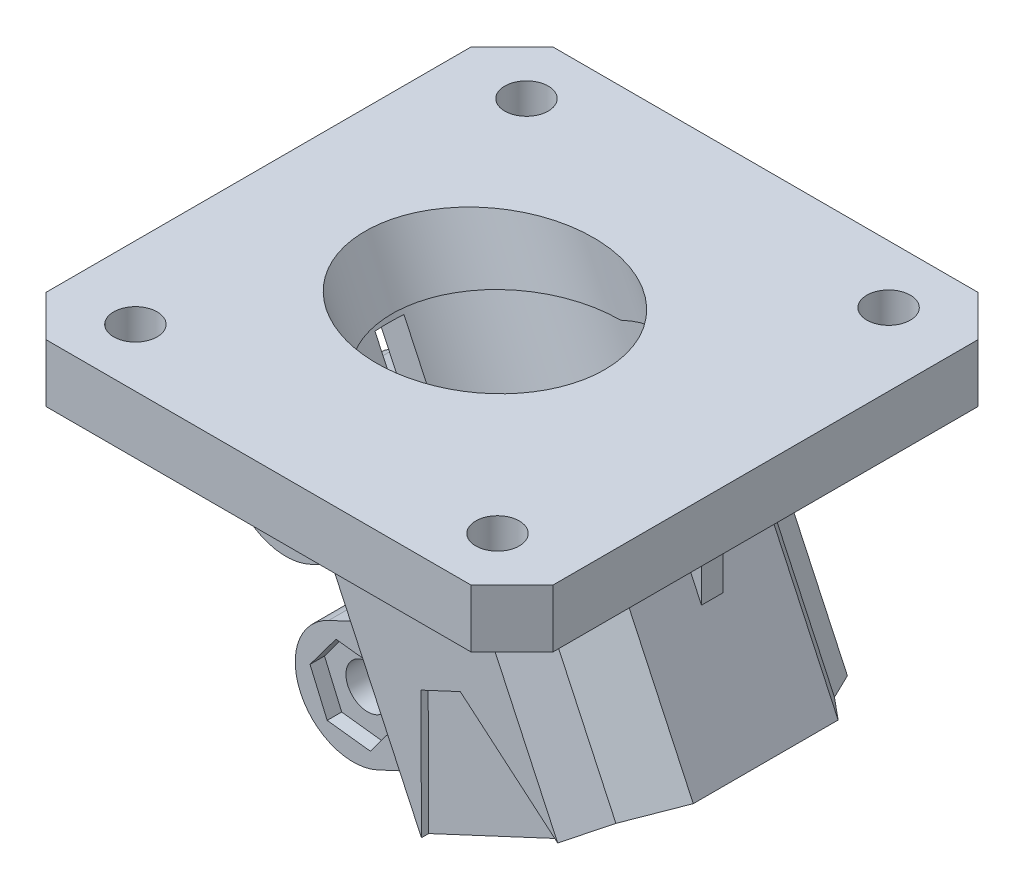
SolidWorks part; units mm, degrees
ref_plane "Front Plane" through (0, 0, 0) normal (0, 0, 1) x (1, 0, 0)
ref_plane "Top Plane" through (0, 0, 0) normal (0, 1, 0) x (1, 0, 0)
ref_plane "Right Plane" through (0, 0, 0) normal (1, 0, 0) x (0, 0, -1)
sketch "Sketch1" plane through (0, 0, 0) normal (0, 1, 0) x (1, 0, 0)
  line L0 (-17.5, 14.6716) -> (-14.6716, 17.5)
  line L1 (14.6716, -17.5) -> (-14.6716, -17.5)
  line L2 (17.5, -14.6716) -> (17.5, 14.6716)
  line L3 (14.6716, 17.5) -> (-14.6716, 17.5)
  line L4 (-17.5, -14.6716) -> (-17.5, 14.6716)
  line L5 (17.5, -17.5) -> (-17.5, 17.5) construction
  line L6 (17.5, 17.5) -> (-17.5, -17.5) construction
  line L7 (14.6716, 17.5) -> (17.5, 14.6716)
  line L8 (17.5, -14.6716) -> (14.6716, -17.5)
  line L9 (-14.6716, -17.5) -> (-17.5, -14.6716)
  point P0 (0, 0)
  point P17 (0, 0)
  dimension "D1" = 35
  dimension "D2" = 35
  dimension "D3" = 4
  dimension "D4" = 4
extrude "Boss-Extrude1" add sketch "Sketch1" along normal blind 4
sketch "Sketch2" plane through (0, 4, 0) normal (0, 1, 0) x (1, 0, 0)
  line L0 (-12.5, 13.5) -> (-12.5, -13.5) construction
  line L1 (-12.5, 13.5) -> (12.5, 13.5) construction
  circle A0 centre (-12.5, 13.5) radius 1.5
  circle A1 centre (12.5, 13.5) radius 1.5
  circle A2 centre (-12.5, -13.5) radius 1.5
  circle A3 centre (12.5, -13.5) radius 1.5
  point P8 (-12.5, 0)
  point P9 (0, 13.5)
  dimension "D3" = 3
  dimension "D4" = 3
  dimension "D5" = 3
  dimension "D6" = 3
  dimension "D1" = 25
  dimension "D2" = 27
  dimension "D7" = 27
  dimension "D8" = 25
extrude "Cut-Extrude1" cut sketch "Sketch2" against normal through all
sketch "Sketch3" plane through (0, 0, 0) normal (0, 0, 1) x (1, 0, 0)
  line L0 (-14.6716, 0) -> (14.6716, 0) construction
  line L2 (-14.6716, 0) -> (14.6716, 0)
  line L3 (0, 0) -> (8.4524, -18.1262)
  dimension "D1" = 65
  dimension "D2" = 20
ref_plane "Plane1" through (8.4524, -18.1262, 0) normal (0.4226, -0.9063, 0) x (-0.9063, -0.4226, 0)
sketch "Sketch4" plane through (8.4524, -18.1262, 0) normal (0.4226, -0.9063, 0) x (-0.9063, -0.4226, 0)
  line L0 (10, 5) -> (10, -5)
  line L1 (10, 5) -> (6.9136, 7.5444)
  line L2 (6.9136, 7.5444) -> (5.1902, 10)
  line L5 (0, 0) -> (10, 0) construction
  line L6 (0, 0) -> (0, 9) construction
  line L7 (-10, 5) -> (-10, -5)
  line L8 (-10, 5) -> (-6.9136, 7.5444)
  line L9 (-6.9136, 7.5444) -> (-5.1902, 10)
  line L11 (10, -5) -> (6.9136, -7.5444)
  line L12 (6.9136, -7.5444) -> (5.1902, -10)
  line L16 (-6.9136, -7.5444) -> (-5.1902, -10)
  line L17 (-10, -5) -> (-6.9136, -7.5444)
  line L18 (-5.1902, 10) -> (5.1902, 10)
  line L19 (-5.1902, -10) -> (5.1902, -10)
  circle A0 centre (0, 0) radius 8
  point P6 (10, 0)
  point P23 (-10, 0)
  dimension "D1" = 16
  dimension "D2" = 10
  dimension "D3" = 10
  dimension "D4" = 3
  dimension "D6" = 4
  dimension "D7" = 10
extrude "Boss-Extrude2" add sketch "Sketch4" against normal up to surface (16.2695 mm away) up to face at (12.5, 0, -12)
sketch "Sketch5" plane through (8.4524, -18.1262, 0) normal (0.4226, -0.9063, 0) x (-0.9063, -0.4226, 0)
  circle A0 centre (0, 0) radius 8 construction
  circle A1 centre (0, 0) radius 8
extrude "Cut-Extrude2" cut sketch "Sketch5" against normal blind 20
sketch "Sketch7" plane through (0, 0, 0) normal (0, 0, 1) x (1, 0, 0)
  line L0 (11.0338, 0) -> (17.5154, -13.9) construction
  line L1 (11.0338, 0) -> (13.8316, -6)
  line L2 (-14.6716, 0) -> (14.6716, 0) construction
  line L3 (11.0338, 0) -> (13.8316, 0)
  line L4 (13.8316, 0) -> (13.8316, -6)
  dimension "D1" = 6
extrude "Boss-Extrude3" add sketch "Sketch7" along normal blind 0.75 and the other way blind 0.75
sketch "Sketch8" plane through (0, 0, 0) normal (0, 0, 1) x (1, 0, 0)
  line L0 (-11.0338, 0) -> (-0.6107, -22.3523) construction
  line L1 (-11.0338, 0) -> (-0.6107, -22.3523)
  line L2 (-14.6716, 0) -> (14.6716, 0) construction
  line L3 (-14.6716, 0) -> (14.6716, 0)
  line L4 (-8.9207, -4.5315) -> (-12.0928, -6.0107)
  line L5 (-9.1344, -12.3549) -> (-5.9624, -10.8757)
  line L6 (-7.444, -15.9801) -> (-4.2719, -14.5009)
  line L7 (-4.4856, -22.3242) -> (-1.3136, -20.8451)
  line L8 (2.1865, -21.048) -> (-0.6107, -22.3523) construction
  circle A0 centre (-10.6136, -9.1828) radius 3.5
  circle A1 centre (-5.9648, -19.1522) radius 3.5
  circle A2 centre (-10.6136, -9.1828) radius 1.5
  circle A3 centre (-5.9648, -19.1522) radius 1.5
  dimension "D1" = 7
  dimension "D2" = 7
  dimension "D3" = 4
  dimension "D9" = 3
  dimension "D10" = 3
  dimension "D4" = 90
  dimension "D5" = 90
  dimension "D6" = 90
  dimension "D7" = 1.6631
  dimension "D8" = 5
extrude "Boss-Extrude4" add sketch "Sketch8" against normal blind 4 contours A0 A2 | A0 L1 L4 | A0 L5 L1 | A1 A3 | A1 L1 L6 | A1 L7 L1 region at (-4.65, -15.5399, 0) region at (-7.0013, -10.4976, 0) region at (-9.2988, -5.5705, 0) region at (-7.2932, -8.4467, 0) region at (-2.3525, -20.4669, 0) region at (-2.6444, -18.4161, 0)
sketch "Sketch9" plane through (0, 0, 0) normal (0, 0, 1) x (1, 0, 0)
  line L0 (-12.3711, -5.5896) -> (-9.1598, -4.0188)
  line L1 (-11.0338, 0) -> (-0.6107, -22.3523) construction
  line L2 (-9.1598, -4.0188) -> (-5.7511, -11.3288)
  line L3 (-5.7511, -11.3288) -> (-8.9231, -12.808)
  line L4 (-7.6553, -15.5269) -> (-4.4832, -14.0478)
  line L5 (-4.4832, -14.0478) -> (-1.1023, -21.2982)
  line L6 (-1.1023, -21.2982) -> (-4.2743, -22.7774)
  circle A0 centre (-5.9648, -19.1522) radius 1.5 construction
  circle A1 centre (-10.6136, -9.1828) radius 1.5 construction
  circle A2 centre (-5.9648, -19.1522) radius 1.5
  circle A3 centre (-10.6136, -9.1828) radius 1.5
  arc A4 (-12.3711, -5.5896) -> (-8.9231, -12.808) centre (-10.6136, -9.1828) ccw
  arc A5 (-7.6553, -15.5269) -> (-4.2743, -22.7774) centre (-5.9648, -19.1522) ccw
  dimension "D1" = 8
  dimension "D2" = 8
  dimension "D3" = 90
  dimension "D4" = 90
extrude "Boss-Extrude5" add sketch "Sketch9" along normal blind 5
sketch "Sketch10" plane through (-9.0631, -4.2262, 0) normal (-0.9063, -0.4226, 0) x (0, 0, 1)
  line L0 (-1, -20) -> (-1, 3)
  line L1 (-1, 3) -> (1, 3)
  line L2 (1, 3) -> (1, -20)
  line L3 (0, -20) -> (0, -7.3369) construction
  line L4 (5, -20) -> (5, -18.8369)
  line L5 (5, 4.6631) -> (-5, 4.6631)
  line L6 (-5, 4.6631) -> (-5, -20)
  line L7 (-5, -20) -> (5, -20)
  line L11 (-1, -20) -> (1, -20)
  line L12 (0, -0.3369) -> (0, 2.9931) construction
  line L32 (-4, -0.3369) -> (0, -0.3369)
  line L34 (0, -0.3369) -> (0, 0.2288)
  line L36 (0, 0.2288) -> (5, 0.2288)
  line L38 (5, 0.2288) -> (5, 4.6631)
  line L40 (5, -18.8369) -> (0, -18.8369)
  line L42 (0, -18.8369) -> (0, -18.3369)
  line L44 (0, -18.3369) -> (-4, -18.3369)
  line L46 (-4, -18.3369) -> (-4, -11.3369)
  line L48 (-4, -11.3369) -> (0, -11.3369)
  line L50 (0, -11.3369) -> (0, -10.8369)
  line L52 (0, -10.8369) -> (5, -10.8369)
  line L54 (5, -10.8369) -> (5, -7.8369)
  line L56 (5, -7.8369) -> (0, -7.8369)
  line L58 (0, -7.8369) -> (0, -7.3369)
  line L60 (0, -7.3369) -> (-4, -7.3369)
  line L62 (-4, -7.3369) -> (-4, -0.3369)
  dimension "D2" = 1
  dimension "D3" = 1
  dimension "D4" = 23
  dimension "D1" = 0
extrude "Cut-Extrude3" cut sketch "Sketch10" against normal up to surface and the other way through all up to face at (-0.7883, 1.6905, 0)
sketch "Sketch11" plane through (0, 0, 10) normal (0, 0, 1) x (1, 0, 0)
  line L0 (8.4524, -18.1262) -> (0, 0) construction
  line L1 (13.1563, -15.9327) -> (3.7485, -20.3196) construction
  line L2 (3.7485, -20.3196) -> (3.712, -11.5096)
  line L3 (3.712, -11.5096) -> (6.4309, -10.2418)
  line L4 (13.1563, -15.9327) -> (6.4309, -10.2418)
  line L5 (3.7485, -20.3196) -> (13.1563, -15.9327)
  point P11 (5.0714, -10.8757)
  dimension "D1" = 8
  dimension "D2" = 3
extrude "Cut-Extrude4" cut sketch "Sketch11" against normal blind 0.5
sketch "Sketch12" plane through (0, 0, -10) normal (0, 0, -1) x (-1, 0, 0)
  line L0 (-8.4524, -18.1262) -> (0, 0) construction
  line L1 (-3.7485, -20.3196) -> (-13.1563, -15.9327) construction
  line L2 (-13.1563, -15.9327) -> (-6.4309, -10.2418)
  line L3 (-6.4309, -10.2418) -> (-3.712, -11.5096)
  line L4 (-3.7485, -20.3196) -> (-3.712, -11.5096)
  point P11 (-5.0714, -10.8757)
  dimension "D1" = 8
  dimension "D2" = 3
extrude "Cut-Extrude5" cut sketch "Sketch12" against normal blind 0.5 and the other way through all
sketch "Sketch13" plane through (0, 0, 0) normal (0.4226, -0.9063, 0) x (0.9063, 0.4226, 0)
  circle A0 centre (0, 0) radius 7.5
  dimension "D1" = 15
extrude "Cut-Extrude6" cut sketch "Sketch13" against normal through all
sketch "Sketch14" plane through (0, 0, 5) normal (0, 0, 1) x (1, 0, 0)
  line L0 (-9.3801, -11.9065) -> (-11.8235, -6.4266)
  line L1 (-12.3638, -11.5946) -> (-8.8398, -6.7385)
  line L2 (-7.6181, -9.4784) -> (-13.5855, -8.8546)
  line L3 (-11.8235, -6.4266) -> (-13.5855, -8.8546)
  line L4 (-13.5855, -8.8546) -> (-12.3638, -11.5946)
  line L5 (-12.3638, -11.5946) -> (-9.3801, -11.9065)
  line L6 (-9.3801, -11.9065) -> (-7.6181, -9.4784)
  line L7 (-7.6181, -9.4784) -> (-8.8398, -6.7385)
  line L8 (-8.8398, -6.7385) -> (-11.8235, -6.4266)
  line L9 (-4.779, -21.9079) -> (-7.1506, -16.3965)
  line L10 (-2.9854, -19.5031) -> (-8.9442, -18.8012)
  line L11 (-7.7584, -21.5569) -> (-4.1712, -16.7474)
  line L12 (-7.1506, -16.3965) -> (-8.9442, -18.8012)
  line L13 (-8.9442, -18.8012) -> (-7.7584, -21.5569)
  line L14 (-7.7584, -21.5569) -> (-4.779, -21.9079)
  line L15 (-4.779, -21.9079) -> (-2.9854, -19.5031)
  line L16 (-2.9854, -19.5031) -> (-4.1712, -16.7474)
  line L17 (-4.1712, -16.7474) -> (-7.1506, -16.3965)
  point P5 (-10.6018, -9.1665)
  point P8 (-10.6018, -9.1665)
  point P11 (-10.6018, -9.1665)
  point P12 (-10.6018, -9.1665)
  point P16 (-5.9648, -19.1522)
  point P19 (-5.9648, -19.1522)
  point P22 (-5.9648, -19.1522)
  circle M11 centre (-10.6136, -9.1828) radius 1.5
  dimension "D1" = 6
  dimension "D2" = 6
  dimension "D3" = 6
  dimension "D4" = 60
  dimension "D5" = 60
  dimension "D6" = 60
  dimension "D7" = 6
  dimension "D8" = 6
  dimension "D9" = 6
  dimension "D10" = 60
  dimension "D11" = 60
  dimension "D12" = 60
extrude "Cut-Extrude7" cut sketch "Sketch14" against normal blind 1 contours L0 L3 L2 M11 | L1 L8 L0 M11 | L2 L7 L1 M11 | L0 L6 L2 M11 | L1 L5 L0 M11 | L2 L4 L1 M11 | L9 L12 L10 | L11 L17 L9 | L10 L16 L11 | L9 L15 L10 | L11 L14 L9 | L10 L13 L11 region at (-10.8167, -11.2302, 5) region at (-8.9266, -10.3803, 5) region at (-12.4971, -10.0108, 5) region at (-8.7182, -8.3258, 5) region at (-12.2752, -7.9503, 5) region at (-10.3866, -7.1151, 5) region at (-6.1674, -20.8723, 5) region at (-4.5764, -20.1877, 5) region at (-7.3532, -18.1166, 5) region at (-4.3738, -18.4675, 5) region at (-7.5558, -19.8368, 5) region at (-5.7622, -17.432, 5)
